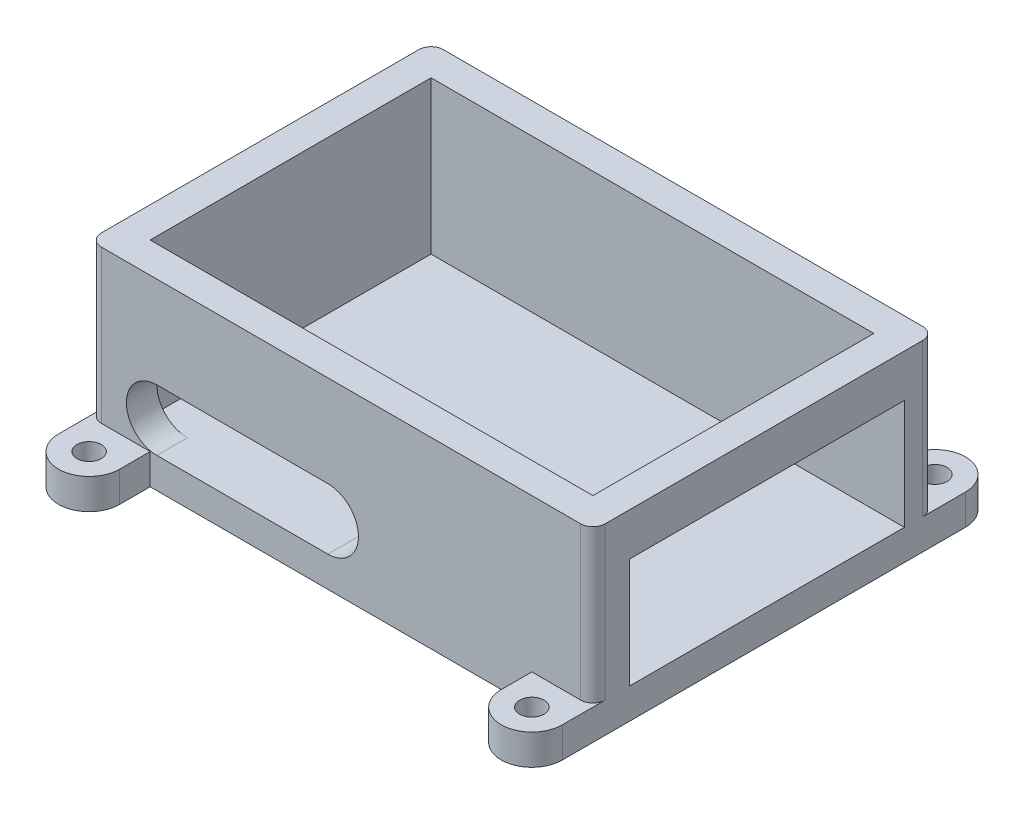
SolidWorks part; units mm, degrees
ref_plane "Front Plane" through (0, 0, 0) normal (0, 0, 1) x (1, 0, 0)
ref_plane "Top Plane" through (0, 0, 0) normal (0, 1, 0) x (1, 0, 0)
ref_plane "Right Plane" through (0, 0, 0) normal (1, 0, 0) x (0, 0, -1)
sketch "Sketch1" plane through (0, 0, 0) normal (0, 1, 0) x (1, 0, 0)
  line L1 (52.3875, -35.56) -> (-52.3875, -35.56)
  line L2 (52.3875, -35.56) -> (52.3875, 35.56)
  line L3 (52.3875, 35.56) -> (-52.3875, 35.56)
  line L4 (-52.3875, -35.56) -> (-52.3875, 35.56)
  line L5 (52.3875, -35.56) -> (-52.3875, 35.56) construction
  line L6 (52.3875, 35.56) -> (-52.3875, -35.56) construction
  line L7 (46.0375, -29.21) -> (-46.0375, -29.21)
  line L8 (46.0375, -29.21) -> (46.0375, 29.21)
  line L9 (46.0375, 29.21) -> (-46.0375, 29.21)
  line L10 (-46.0375, -29.21) -> (-46.0375, 29.21)
  line L11 (46.0375, -29.21) -> (-46.0375, 29.21) construction
  line L12 (46.0375, 29.21) -> (-46.0375, -29.21) construction
  point P0 (0, 0)
  point P6 (0, 0)
  dimension "D1" = 6.35
  dimension "D2" = 6.35
  dimension "D3" = 92.075
  dimension "D4" = 58.42
extrude "Boss-Extrude1" add sketch "Sketch1" along normal blind 6.35 contours L10 L7 L8 L9 | L4 L1 L2 L3 L7 L10 L9 L8 region at (0, 0, 34.2937) region at (0, 0, 0)
extrude "Boss-Extrude2" add sketch "Sketch1<3>" along normal blind 38.1
sketch "Sketch1<3>" plane through (0, 0, 0) normal (0, 1, 0) x (1, 0, 0) same geometry as "Sketch1"
sketch "Sketch2" plane through (0, 0, 35.56) normal (0, 0, 1) x (1, 0, 0)
  line L0 (-38.2837, 12.7) -> (-2.7237, 12.7) construction
  line L1 (-38.2837, 19.05) -> (-2.7237, 19.05)
  line L2 (-38.2837, 6.35) -> (-2.7237, 6.35)
  line L3 (46.0375, 6.35) -> (-46.0375, 6.35) construction
  arc A0 (-38.2837, 19.05) -> (-38.2837, 6.35) centre (-38.2837, 12.7) ccw
  arc A1 (-2.7237, 6.35) -> (-2.7237, 19.05) centre (-2.7237, 12.7) ccw
  point P2 (-20.5037, 12.7)
  point P7 (-19.1218, 22.0369)
  point P10 (-36.04, 12.71)
  point P12 (-19.24, 12.75)
  point P13 (-19.8368, 12.45)
  point P14 (-2.69, 12.3)
  dimension "D1" = 6.35
  dimension "D2" = 35.56
extrude "Cut-Extrude1" cut sketch "Sketch2" against normal up to next
sketch "Sketch3" plane through (52.3875, 0, 0) normal (1, 0, 0) x (0, 0, -1)
  line L0 (29.21, 38.1) -> (29.21, 6.35) construction
  line L1 (-27.94, 29.21) -> (29.21, 29.21)
  line L2 (-27.94, 29.21) -> (-27.94, 6.35)
  line L3 (-27.94, 6.35) -> (29.21, 6.35)
  line L4 (29.21, 29.21) -> (29.21, 6.35)
  line L5 (29.21, 6.35) -> (-29.21, 6.35) construction
  line L6 (-35.56, 38.1) -> (-35.56, 0) construction
  point P6 (-27.9049, 29.1748)
  dimension "D1" = 7.62
  dimension "D2" = 22.86
extrude "Cut-Extrude2" cut sketch "Sketch3" against normal up to next
sketch "Sketch4" plane through (0, 0, 0) normal (0, -1, 0) x (1, 0, 0)
  line L0 (52.3875, 35.56) -> (-52.3875, 35.56) construction
  line L1 (-52.3875, 35.56) -> (-52.3875, -35.56) construction
  line L2 (52.3875, 35.56) -> (52.3875, -35.56) construction
  line L3 (52.3875, -35.56) -> (-52.3875, -35.56) construction
  line L4 (-39.6875, 41.91) -> (-39.6875, 35.56)
  line L5 (-52.3875, 41.91) -> (-52.3875, 35.56)
  line L6 (-52.3875, 35.56) -> (-39.6875, 35.56)
  line L7 (39.6875, 41.91) -> (39.6875, 35.56)
  line L8 (39.6875, 35.56) -> (52.3875, 35.56)
  line L9 (52.3875, 41.91) -> (52.3875, 35.56)
  line L10 (-52.3875, -41.91) -> (-52.3875, -35.56)
  line L11 (-52.3875, -35.56) -> (-39.6875, -35.56)
  line L12 (-39.6875, -35.56) -> (-39.6875, -41.91)
  line L13 (39.6875, -41.91) -> (39.6875, -35.56)
  line L14 (39.6875, -35.56) -> (52.3875, -35.56)
  line L15 (52.3875, -35.56) -> (52.3875, -41.91)
  arc A0 (-39.6875, 41.91) -> (-52.3875, 41.91) centre (-46.0375, 41.91) ccw
  arc A1 (52.3875, 41.91) -> (39.6875, 41.91) centre (46.0375, 41.91) ccw
  arc A2 (-52.3875, -41.91) -> (-39.6875, -41.91) centre (-46.0375, -41.91) ccw
  arc A3 (39.6875, -41.91) -> (52.3875, -41.91) centre (46.0375, -41.91) ccw
  dimension "D2" = 12.7
  dimension "D1" = 6.35
extrude "Boss-Extrude3" add sketch "Sketch4" against normal blind 6.35
sketch "Sketch5" plane through (0, 6.35, 0) normal (0, 1, 0) x (1, 0, 0)
  circle A0 centre (-46.0375, 41.91) radius 2.54
  circle A1 centre (46.0375, 41.91) radius 2.54
  circle A2 centre (46.0375, -41.91) radius 2.54
  circle A3 centre (-46.0375, -41.91) radius 2.54
  dimension "D1" = 5.08
extrude "Cut-Extrude3" cut sketch "Sketch5" against normal up to next
fillet "Fillet1" radius 2.54 4 edges at (52.3875, 22.225, -35.56) (52.3875, 22.225, 35.56) (-52.3875, 22.225, -35.56) (-52.3875, 22.225, 35.56)
